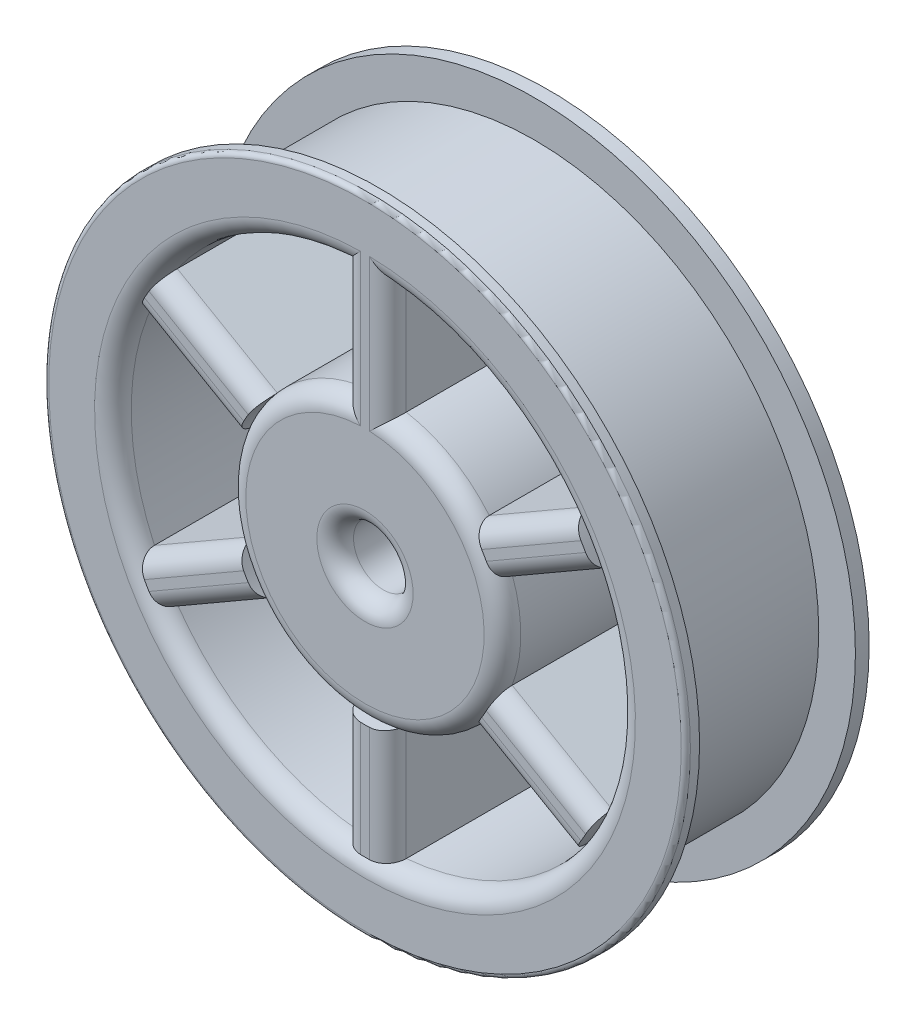
SolidWorks part; units mm, degrees
ref_plane "Front" through (0, 0, 0) normal (0, 0, 1) x (1, 0, 0)
ref_plane "Top" through (0, 0, 0) normal (0, 1, 0) x (1, 0, 0)
ref_plane "Right" through (0, 0, 0) normal (1, 0, 0) x (0, 0, -1)
sketch "Sketch1" plane through (0, 0, 0) normal (0, 0, 1) x (1, 0, 0)
  circle A0 centre (0, 0) radius 15
  circle A3 centre (0, 0) radius 3.25
  dimension "D1" = 30
  dimension "D2" = 6.5
extrude "Boss-Extrude1" add sketch "Sketch1" along normal blind 20
sketch "Sketch2" plane through (0, 0, 0) normal (0, 0, 1) x (1, 0, 0)
  circle A0 centre (0, 0) radius 35
  circle A1 centre (0, 0) radius 27.5
  dimension "D1" = 70
  dimension "D2" = 7.5
extrude "Boss-Extrude2" add sketch "Sketch2" along normal blind 20
sketch "Sketch4" plane through (0, 0, 0) normal (0, 0, 1) x (1, 0, 0)
  line L0 (0, 27.5) -> (0, 15) construction
  line L1 (0, -50) -> (0, 50) construction
  line L2 (-2.5, 27.3861) -> (-2.5, 14.7902)
  line L3 (2.5, 14.7902) -> (2.5, 27.3861)
  circle A0 centre (0, 0) radius 27.5 construction
  circle A1 centre (0, 0) radius 15 construction
  arc A2 (-2.5, 14.7902) -> (2.5, 14.7902) centre (0, 0) cw
  arc A3 (-2.5, 27.3861) -> (2.5, 27.3861) centre (0, 0) cw
  dimension "D1" = 5
extrude "Boss-Extrude3" add sketch "Sketch4" along normal up to surface (20 mm away) up to face at (35, 0, 20)
fillet "Fillet2" radius 2 2 edges at (2.5, 21.0882, 20) (-2.5, 21.0882, 20)
fillet "Fillet3" radius 0.5 1 edges at (35, 0, 20)
fillet "Fillet4" radius 2 3 edges at (3.25, 0, 20) (0, -27.5, 20) (0, -15, 20)
sketch "Sketch5" plane through (0, 0, 0) normal (1, 0, 0) x (0, 0, -1)
  line L0 (0, 0) -> (-32.2104, 0) construction
pattern_circular "CirPattern1" count 6 over 360 about axis through (0, 0, 0) along (0, 0, 1) of "Boss-Extrude3", "Fillet2" reverse direction yes
sketch "Sketch6" plane through (0, 0, 0) normal (1, 0, 0) x (0, 0, -1)
  line L0 (0, 35) -> (-19.5, 35) construction
  line L1 (-1.5, 35) -> (-18.5, 35)
  line L2 (-1.5, 35) -> (-1.5, 31)
  line L3 (-1.5, 31) -> (-18.5, 31)
  line L4 (-18.5, 35) -> (-18.5, 31)
  line L5 (0, -35) -> (0, 35) construction
  line L6 (-20, 35) -> (-20, -35) construction
  dimension "D1" = 1.5
  dimension "D2" = 1.5
  dimension "D3" = 4
revolve "Cut-Revolve1" cut sketch "Sketch6" angle 360 about L0
